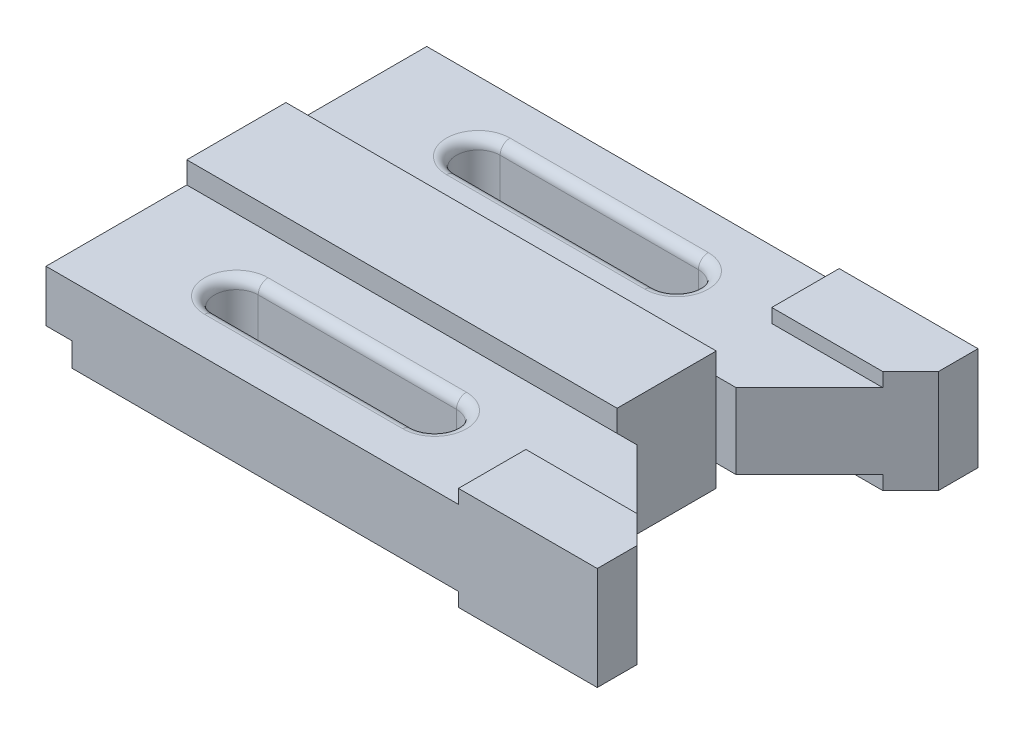
SolidWorks part; units mm, degrees
material "Alliage 1060"
ref_plane "Plan de face" through (0, 0, 0) normal (0, 0, 1) x (1, 0, 0)
ref_plane "Plan de dessus" through (0, 0, 0) normal (0, 1, 0) x (1, 0, 0)
ref_plane "Plan de droite" through (0, 0, 0) normal (1, 0, 0) x (0, 0, -1)
sketch "Esquisse1" plane through (0, 0, 0) normal (0, 1, 0) x (1, 0, 0)
  line L0 (0, 0) -> (-143.5103, 0) construction
  line L1 (0, -12.5) -> (0, 12.5)
  line L2 (-108.5, 12.5) -> (5, 12.5)
  line L3 (5, 12.5) -> (30.5, 38)
  line L4 (30.5, 38) -> (30.5, 48)
  line L5 (30.5, 48) -> (-108.5, 48)
  line L6 (-108.5, 48) -> (-108.5, -48)
  line L7 (-78, -30.5) -> (-28, -30.5) construction
  line L8 (-78, 30.5) -> (-28, 30.5) construction
  line L9 (-78, 36) -> (-28, 36)
  line L10 (-78, 25) -> (-28, 25)
  line L11 (23.5, 31) -> (-4.5, 31)
  line L12 (-4.5, 31) -> (-4.5, 48)
  line L13 (-78, -36) -> (-28, -36)
  line L14 (-78, -25) -> (-28, -25)
  line L15 (-4.5, -31) -> (-4.5, -48)
  line L16 (23.5, -31) -> (-4.5, -31)
  line L17 (30.5, -48) -> (-108.5, -48)
  line L18 (30.5, -38) -> (30.5, -48)
  line L19 (5, -12.5) -> (30.5, -38)
  line L20 (-108.5, -12.5) -> (5, -12.5)
  arc A0 (-78, 36) -> (-78, 25) centre (-78, 30.5) ccw
  arc A1 (-28, 25) -> (-28, 36) centre (-28, 30.5) ccw
  arc A2 (-78, -36) -> (-78, -25) centre (-78, -30.5) cw
  arc A3 (-28, -25) -> (-28, -36) centre (-28, -30.5) cw
  point P12 (-53, 30.5)
  point P24 (-53, -30.5)
  point P33 (-108.5, 0)
  dimension "D3" = 5.5
  dimension "D1" = 96
  dimension "D2" = 17.5
  dimension "D4" = 50
  dimension "D5" = 30.5
  dimension "D6" = 10
  dimension "D7" = 35.5
  dimension "D8" = 17
  dimension "D9" = 35
  dimension "D10" = 139
  dimension "D11" = 45
  dimension "D12" = 30.5
extrude "Boss.-Extru.1" add sketch "Esquisse1" along normal mid plane 30 contours L6 L20 L1 L2 region at (-54.25, 0, 0)
extrude "Boss.-Extru.2" add sketch "Esquisse1<3>" along normal offset from surface 5.5 and the other way offset from surface 5.5 contours L20 L6 L17 L15 L16 L19 L14 A3 L13 A2 | L11 L12 L5 L6 L2 L3 A1 L10 A0 L9 region at (2.5, 0, 13.8669) region at (-54.25, 0, -13.8669) up to face at (-54.25, 15, 0) other way up to face at (-54.25, -15, 0)
sketch "Esquisse1<3>" plane through (0, 0, 0) normal (0, 1, 0) x (1, 0, 0) same geometry as "Esquisse1"
extrude "Boss.-Extru.3" add sketch "Esquisse1<4>" along normal mid plane 26 contours L12 L11 L3 L4 L5 | L19 L16 L15 L17 L18 region at (12.3487, 0, 39.7648) region at (12.3487, 0, -39.7648)
sketch "Esquisse1<4>" plane through (0, 0, 0) normal (0, 1, 0) x (1, 0, 0) same geometry as "Esquisse1"
sketch "Esquisse2" plane through (0, 0, 0) normal (0, 0, 1) x (1, 0, 0)
  line L0 (-108.5, 9.5) -> (-108.5, -9.5) construction
  line L1 (-108.5, -3.5) -> (-102, -3.5)
  line L2 (-108.5, -3.5) -> (-108.5, -15)
  line L3 (-108.5, -15) -> (-102, -15)
  line L4 (-102, -3.5) -> (-102, -15)
  line L5 (-108.5, -15) -> (0, -15) construction
  dimension "D1" = 11.5
  dimension "D2" = 6.5
extrude "Enlèv. mat.-Extru.1" cut sketch "Esquisse2" against normal through all and the other way through all
fillet "Congé1" radius 2.5 16 edges at (-22.5, -9.5, 30.5) (-53, -9.5, 25) (-83.5, -9.5, 30.5) (-53, -9.5, -36) (-83.5, -9.5, -30.5) (-53, -9.5, -25) (-53, 9.5, 36) (-22.5, 9.5, 30.5) (-53, 9.5, 25) (-53, 9.5, -36) (-22.5, 9.5, -30.5) (-53, 9.5, -25) (-53, -9.5, 36) (-22.5, -9.5, -30.5) (-83.5, 9.5, 30.5) (-83.5, 9.5, -30.5)
equation "\"A\" = 139"
equation "\"B\"= 50"
equation "\"C\" = 45deg"
equation "\"D4@Esquisse1\"=\"B\""
equation "\"D10@Esquisse1\"=\"A\""
equation "\"D11@Esquisse1\"=\"C\""
